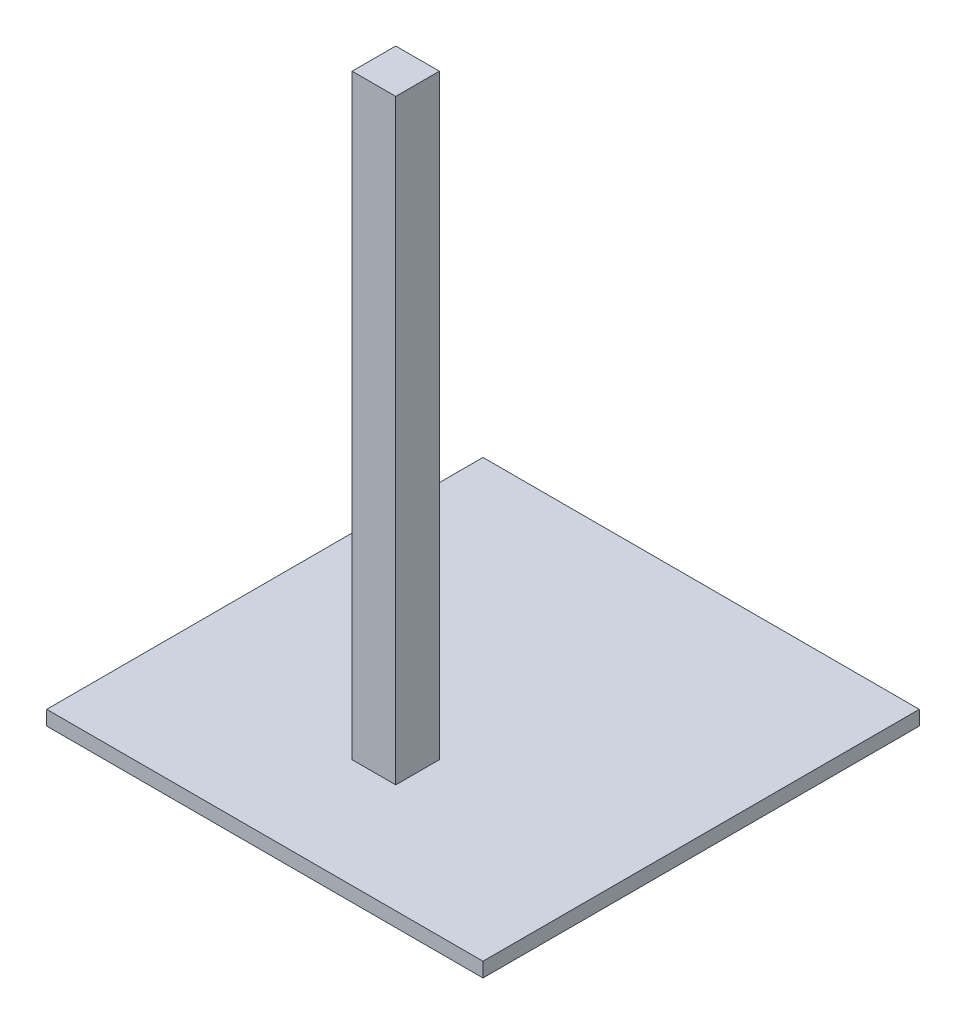
SolidWorks part; units mm, degrees
ref_plane "Front Plane" through (0, 0, 0) normal (0, 0, 1) x (1, 0, 0)
ref_plane "Top Plane" through (0, 0, 0) normal (0, 1, 0) x (1, 0, 0)
ref_plane "Right Plane" through (0, 0, 0) normal (1, 0, 0) x (0, 0, -1)
sketch "Sketch1" plane through (0, 0, 0) normal (0, 1, 0) x (1, 0, 0)
  line L1 (-38.1, -38.1) -> (38.1, -38.1)
  line L2 (-38.1, -38.1) -> (-38.1, 38.1)
  line L3 (-38.1, 38.1) -> (38.1, 38.1)
  line L4 (38.1, -38.1) -> (38.1, 38.1)
  line L5 (-38.1, -38.1) -> (38.1, 38.1) construction
  line L6 (-38.1, 38.1) -> (38.1, -38.1) construction
  point P0 (0, 0)
  dimension "D1" = 76.2
  dimension "D2" = 76.2
extrude "Boss-Extrude1" add sketch "Sketch1" along normal blind 2.54
sketch "Sketch2" plane through (0, 2.54, 0) normal (0, 1, 0) x (1, 0, 0)
  line L1 (-3.81, -11.43) -> (3.81, -11.43)
  line L2 (-3.81, -11.43) -> (-3.81, -19.05)
  line L3 (-3.81, -19.05) -> (3.81, -19.05)
  line L4 (3.81, -11.43) -> (3.81, -19.05)
  line L5 (-3.81, -11.43) -> (3.81, -19.05) construction
  line L6 (-3.81, -19.05) -> (3.81, -11.43) construction
  point P0 (0, -15.24)
  point P5 (0, 0)
  point P6 (0, -16.8513)
  dimension "D1" = 7.62
  dimension "D2" = 15.24
extrude "Boss-Extrude2" add sketch "Sketch2" along normal blind 104.14
